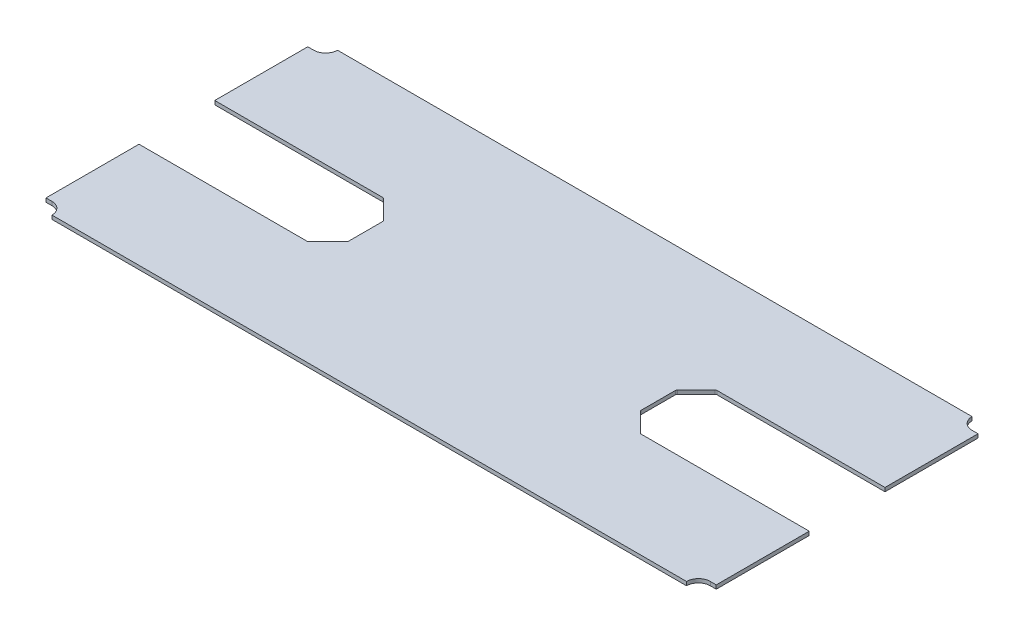
SolidWorks part; units mm, degrees
material "Mahogany"
ref_plane "Front Plane" through (0, 0, 0) normal (0, 0, 1) x (1, 0, 0)
ref_plane "Top Plane" through (0, 0, 0) normal (0, 1, 0) x (1, 0, 0)
ref_plane "Right Plane" through (0, 0, 0) normal (1, 0, 0) x (0, 0, -1)
sketch "Sketch1" plane through (0, 0, 0) normal (0, 1, 0) x (1, 0, 0)
  line L0 (-845, 95.5) -> (-369, 95.5)
  line L1 (-845, 360) -> (845, 360)
  line L2 (-845, 360) -> (-845, -360)
  line L3 (-845, -360) -> (845, -360)
  line L4 (845, 360) -> (845, -360)
  line L5 (-845, 360) -> (845, -360) construction
  line L6 (-845, -360) -> (845, 360) construction
  line L23 (-369, 95.5) -> (-369, -95.5)
  line L24 (-369, -95.5) -> (-845, -95.5)
  line L25 (845, 95.5) -> (369, 95.5)
  line L26 (369, 95.5) -> (369, -95.5)
  line L27 (369, -95.5) -> (845, -95.5)
  line L28 (-845, 330) -> (-830, 330)
  line L29 (0, -360) -> (0, 360) construction
  line L30 (-845, 0) -> (845, 0) construction
  line L31 (-845, -330) -> (-830, -330)
  line L32 (845, 330) -> (830, 330)
  line L33 (845, -330) -> (830, -330)
  arc A0 (-830, 330) -> (-800, 360) centre (-830, 360) ccw
  arc A1 (-830, -330) -> (-800, -360) centre (-830, -360) cw
  arc A2 (830, 330) -> (800, 360) centre (830, 360) cw
  arc A3 (830, -330) -> (800, -360) centre (830, -360) ccw
  point P0 (0, 0)
  point P26 (369, 0)
  point P27 (-369, 0)
  dimension "D6" = 30
  dimension "D4" = 476
  dimension "D5" = 191
  dimension "D2" = 720
  dimension "D1" = 1690
  dimension "D3" = 15
extrude "Boss-Extrude1" add sketch "Sketch1" along normal blind 9.525 contours L27 L26 L25 L4 L1 L2 L0 L23 L24 L3 region at (0, 0, 0)
chamfer "Chamfer1" distance 50 angle 45 4 edges at (369, 4.7625, 95.5) (369, 4.7625, -95.5) (-369, 4.7625, 95.5) (-369, 4.7625, -95.5)
fillet "Fillet2" radius 5 8 edges at (369, 4.7625, -45.5) (369, 4.7625, 45.5) (419, 4.7625, 95.5) (419, 4.7625, -95.5) (-419, 4.7625, 95.5) (-369, 4.7625, 45.5) (-369, 4.7625, -45.5) (-419, 4.7625, -95.5)
equation "\"W\"= 1700"
equation "\"L\"= 760"
equation "\"H\"= 810"
equation "\"ARM_BOLT_SPACING\"= 166"
equation "\"ARM_TO_WALL\"= 300"
equation "\"D4@Sketch1\"=\"ARM_TO_WALL\"+\"ARM_BOLT_SPACING\"+10"
equation "\"D5@Sketch1\"=\"ARM_BOLT_SPACING\"+25"
equation "\"D2@Sketch1\"=\"L\"-40"
equation "\"D1@Sketch1\"=\"W\"-10"
